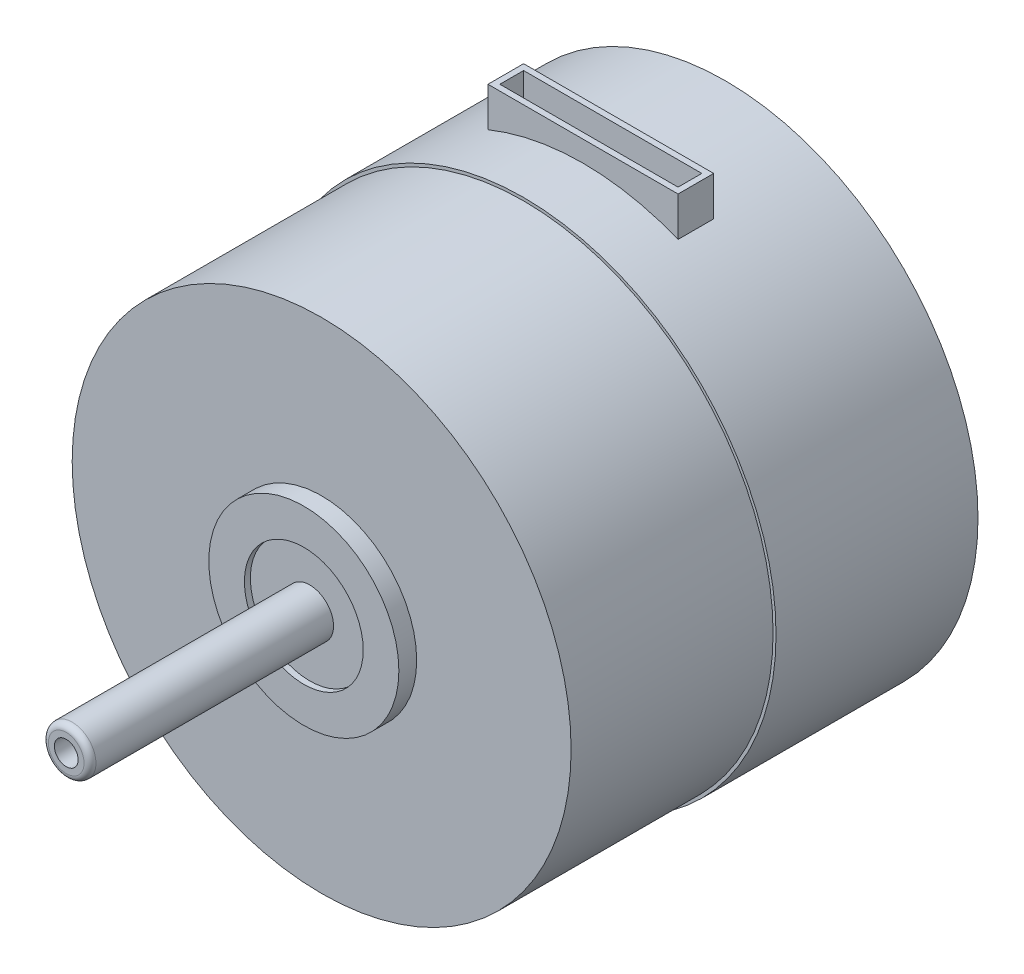
SolidWorks part; units mm, degrees
ref_plane "정면" through (0, 0, 0) normal (0, 0, 1) x (1, 0, 0)
ref_plane "윗면" through (0, 0, 0) normal (0, 1, 0) x (1, 0, 0)
ref_plane "우측면" through (0, 0, 0) normal (1, 0, 0) x (0, 0, -1)
sketch "스케치1" plane through (0, 0, 0) normal (0, 0, 1) x (1, 0, 0)
  circle A0 centre (0, 0) radius 21
  dimension "D1" = 42
extrude "보스-돌출1" add sketch "스케치1" along normal blind 17
sketch "스케치2" plane through (0, 0, 17) normal (0, 0, 1) x (1, 0, 0)
  circle A0 centre (0, 0) radius 8
  dimension "D1" = 16
extrude "보스-돌출2" add sketch "스케치2" along normal blind 1.5
sketch "스케치3" plane through (0, 0, 18.5) normal (0, 0, 1) x (1, 0, 0)
  circle A0 centre (0, 0) radius 3
  dimension "D1" = 6
extrude "보스-돌출3" add sketch "스케치3" along normal blind 20.5
chamfer "모따기1" distance 1 angle 45 1 edges at (3, 0, 39)
thread "나사산1" pitch 1 method cut profile "나사산 프로파일1" start angle 0, offset 0, length 8, pitch 1, diameter 6
ref_plane "평면1" through (-3, 0, 38) normal (0, -1, 0) x (-1, 0, 0)
sketch "나사산 프로파일1" plane through (-3, 0, 38) normal (0, -1, 0) x (-1, 0, 0)
  line L0 (0, 0) -> (0, 1) construction
  line L11 (0, 0) -> (0, 0.875)
  line L12 (0, 0.875) -> (-0.5413, 0.5625)
  line L13 (-0.5413, 0.5625) -> (-0.5413, 0.3125)
  line L15 (-0.5413, 0.3125) -> (0, 0)
  line L17 (-0.5413, 0.4375) -> (0, 0.4375) construction
  point P2 (0, 0)
  dimension "Pitch" = 1
  dimension "Profile_Angle" = 60
  dimension "Profile_Land" = 0.25
  dimension "Profile_Height" = 0.5413
ref_plane "평면2" through (0, 0, 27) normal (0, 0, 1) x (1, 0, 0)
ref_plane "평면3" through (0, 3, 0) normal (0, 1, 0) x (1, 0, 0)
sketch "스케치8" plane through (0, 3, 0) normal (0, 1, 0) x (1, 0, 0)
  line L0 (3, -38) -> (3, -37.5) construction
  line L1 (-3, -38) -> (-3, -37.125) construction
  line L2 (3, -29.625) -> (3, -18.5) construction
  line L3 (-3, -18.5) -> (-3, -29.125) construction
  line L4 (-3, -29.125) -> (-3, -30) construction
  line L5 (3, -38) -> (3, -37.5)
  line L6 (-3, -38) -> (-3, -37.125)
  line L7 (3, -29.625) -> (3, -18.5)
  line L8 (-3, -18.5) -> (-3, -29.125)
  line L9 (-3, -29.125) -> (-3, -30)
  line L10 (-3, -37.125) -> (-3, -30)
  line L11 (3, -37.5) -> (3, -29.625)
  line L13 (-3, -18.5) -> (3, -18.5)
  line L14 (-3, -27) -> (3, -27)
  line L15 (-2, -39) -> (2, -39) construction
  line L16 (-2, -39) -> (2, -39)
  line L17 (-3, -38) -> (-3, -39)
  line L18 (-3, -39) -> (-2, -39)
  line L19 (2, -39) -> (3, -39)
  line L20 (3, -39) -> (3, -38)
  dimension "D1" = 8.5
extrude "컷-돌출1" cut sketch "스케치8" against normal blind 1 contours L14 L8 L9 L10 L6 L5 L11 L7 region at (0, 3, 33)
sketch "Sketch1" plane through (0, 0, 0) normal (0, 1, 0) x (1, 0, 0)
  line L0 (3, -29.625) -> (3, -18.5) construction
  line L1 (-3, -18.5) -> (3, -18.5)
  line L2 (-3, -18.5) -> (-3, -39)
  line L3 (-3, -39) -> (3, -39)
  line L4 (3, -18.5) -> (3, -39)
extrude "Extrude1" cut sketch "Sketch1" against normal through all both and the other way through all
sketch "Sketch2" plane through (0, 0, 18.5) normal (0, 0, 1) x (1, 0, 0)
  circle A0 centre (0, 0) radius 2
  dimension "D1" = 4
extrude "Extrude2" add sketch "Sketch2" along normal blind 20
fillet "Fillet1" radius 0.5 1 edges at (2, 0, 38.5)
sketch "Sketch3" plane through (0, 0, 38.5) normal (0, 0, 1) x (1, 0, 0)
  circle A0 centre (0, 0) radius 1
  dimension "D1" = 2
extrude "Extrude3" cut sketch "Sketch3" against normal blind 2
fillet "Fillet2" radius 0.5 1 edges at (1, 0, 36.5)
sketch "Sketch4" plane through (0, 0, 18.5) normal (0, 0, 1) x (1, 0, 0)
  circle A0 centre (0, 0) radius 5
  circle A1 centre (0, 0) radius 2
  dimension "D1" = 10
  dimension "D2" = 4
extrude "Extrude5" cut sketch "Sketch4" against normal blind 0.5
sketch "Sketch5" plane through (0, 0, 0) normal (0, 0, -1) x (-1, 0, 0)
  circle A0 centre (0, 0) radius 21.25
  dimension "D1" = 42.5
extrude "Extrude7" add sketch "Sketch5" along normal blind 17
ref_plane "Plane1" through (0, 15, 0) normal (0, 1, 0) x (1, 0, 0)
sketch "Sketch6" plane through (0, 15, 0) normal (0, 1, 0) x (1, 0, 0)
  line L1 (-8, 8) -> (8, 8)
  line L2 (-8, 8) -> (-8, 5)
  line L3 (-8, 5) -> (8, 5)
  line L4 (8, 8) -> (8, 5)
  point P4 (0, 5)
  dimension "D1" = 5
  dimension "D2" = 3
  dimension "D3" = 8
extrude "Extrude8" add sketch "Sketch6" along normal blind 8
sketch "Sketch7" plane through (0, 23, 0) normal (0, 1, 0) x (1, 0, 0)
  line L0 (8, 8) -> (-8, 8) construction
  line L1 (-7.5, 7.5) -> (7.5, 7.5)
  line L2 (-7.5, 7.5) -> (-7.5, 5.5)
  line L3 (-7.5, 5.5) -> (7.5, 5.5)
  line L4 (7.5, 7.5) -> (7.5, 5.5)
  line L5 (-8, 8) -> (-8, 5) construction
  line L6 (-8, 5) -> (8, 5) construction
  line L7 (8, 5) -> (8, 8) construction
  dimension "D1" = 0.5
  dimension "D2" = 0.5
  dimension "D3" = 0.5
  dimension "D4" = 0.5
extrude "Extrude9" cut sketch "Sketch7" against normal blind 3
